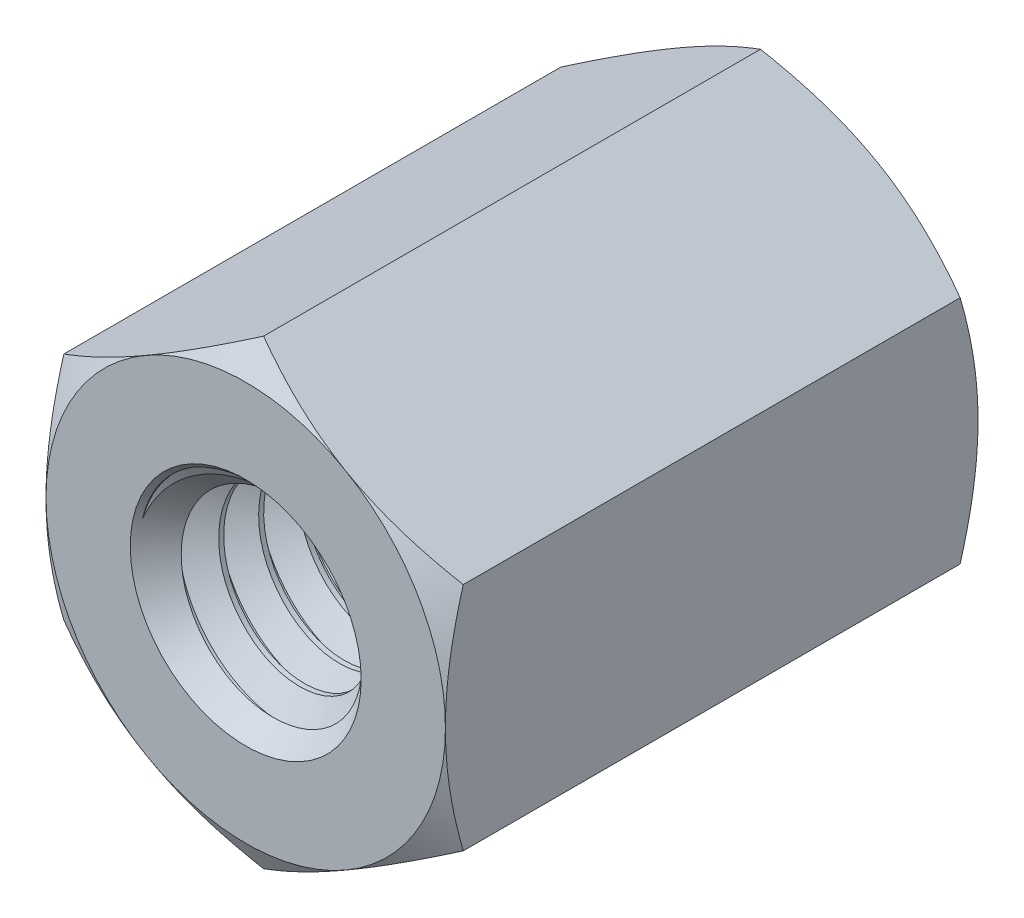
SolidWorks part; units mm, degrees
ref_plane "Front Plane" through (0, 0, 0) normal (0, 0, 1) x (1, 0, 0)
ref_plane "Top Plane" through (0, 0, 0) normal (0, 1, 0) x (1, 0, 0)
ref_plane "Right Plane" through (0, 0, 0) normal (1, 0, 0) x (0, 0, -1)
sketch "Sketch3" plane through (0, 0, 0) normal (1, 0, 0) x (0, 0, -1)
  line L0 (-3, 0) -> (3, 0) construction
  line L1 (0, 2.25) -> (0, -2.25) construction
  line L2 (-3, 1.25) -> (-3, -1.25) construction
  point P2 (-1.8, 0)
  point P3 (1.8, 0)
  dimension "Length" = 6
  dimension "Min Thread Length" = 4.8
  dimension "D1" = 4.8
  dimension "Thread Dia" = 2.5
  dimension "Hex" = 4.5
sketch "Sketch1" plane through (0, 0, 0) normal (0, 0, 1) x (1, 0, 0)
  line L1 (0, 2.5981) -> (-2.25, 1.299)
  line L2 (-2.25, 1.299) -> (-2.25, -1.299)
  line L3 (-2.25, -1.299) -> (0, -2.5981)
  line L4 (0, -2.5981) -> (2.25, -1.299)
  line L5 (2.25, -1.299) -> (2.25, 1.299)
  line L6 (2.25, 1.299) -> (0, 2.5981)
  circle A0 centre (0, 0) radius 2.25 construction
  circle A1 centre (0, 0) radius 1.25
extrude "Extrude1" add sketch "Sketch1" along normal up to vertex (3 mm away) and the other way up to vertex (3 mm away) up to point (0, 0, 3) other way up to point (0, 0, -3)
sketch "Sketch11" plane through (0, 0, -3) normal (0, 0, -1) x (-1, 0, 0)
  circle A0 centre (0, 0) radius 1.25 construction
  circle A1 centre (0, 0) radius 1.25
curve "Helix/Spiral1" pitch 0.45 height 6.45 radius 1.25 centre (0, 0, -3) axis (0, 0, 1) start towards (0, 1, 0) parameters "Pitch"=0.45
sketch "Sketch12" plane through (0, 0, 0) normal (1, 0, 0) x (0, 0, -1)
  line L0 (3.3937, 1.25) -> (3, 1.25)
  line L1 (3.3937, 1.25) -> (3.225, 0.9577)
  line L2 (3.225, 0.9577) -> (3.1687, 0.9577)
  line L3 (3.1687, 0.9577) -> (3, 1.25)
  line L4 (3.1969, 0.9577) -> (3.1969, 1.25) construction
  line L5 (3.3094, 1.1039) -> (3.0844, 1.1039) construction
  dimension "D1" = 0.0563
  dimension "D2" = 0.225
  dimension "D3" = 60
sweep "Sweep1" add profiles "Sketch12" path "Helix/Spiral1"
sketch "Sketch6" plane through (0, 0, -3) normal (0, 0, -1) x (-1, 0, 0)
  line L6 (0, 2.5981) -> (-2.25, 1.299)
  line L7 (-2.25, 1.299) -> (-2.25, -1.299)
  line L8 (-2.25, -1.299) -> (0, -2.5981)
  line L9 (0, -2.5981) -> (2.25, -1.299)
  line L10 (2.25, -1.299) -> (2.25, 1.299)
  line L11 (2.25, 1.299) -> (0, 2.5981)
  line L12 (0, 2.5981) -> (-2.25, 1.299)
  line L13 (-2.25, 1.299) -> (-2.25, -1.299)
  line L14 (-2.25, -1.299) -> (0, -2.5981)
  line L15 (0, -2.5981) -> (2.25, -1.299)
  line L16 (2.25, -1.299) -> (2.25, 1.299)
  line L17 (2.25, 1.299) -> (0, 2.5981)
  dimension "D1" = 0
extrude "Extrude2" cut sketch "Sketch6" along normal through all
sketch "Sketch7" plane through (0, 0, -3) normal (0, 0, -1) x (-1, 0, 0)
  circle A2 centre (0, 0) radius 1.3008
  circle A3 centre (0, 0) radius 1.3008
  dimension "D1" = 0.0508
extrude "Extrude3" cut sketch "Sketch7" against normal through all draft 43
sketch "Sketch8" plane through (0, 0, -3) normal (0, 0, -1) x (-1, 0, 0)
  circle A0 centre (0, 0) radius 2.25 construction
  circle A1 centre (0, 0) radius 2.25
extrude "Extrude4" cut sketch "Sketch8" against normal through all draft 60 flip side to cut
mirror "Mirror1" about plane through (0, 0, 0) normal (0, 0, 1) of "Extrude2", "Extrude3", "Extrude4"
sketch "Sketch9" [suppressed] plane through (0, 0, 0) normal (1, 0, 0) x (0, 0, -1)
  line L1 (-1.2, 1.1353) -> (1.2, 1.1353)
  line L2 (-1.2, 1.1353) -> (-1.2, 0)
  line L3 (-1.2, 0) -> (1.2, 0)
  line L4 (1.2, 1.1353) -> (1.2, 0)
  line L7 (-6, 0) -> (6, 0) construction
revolve "Revolve" [suppressed] add sketch "Sketch9" angle 360 about L0
sketch "Sketch10" [suppressed] plane through (0, 0, 0) normal (1, 0, 0) x (0, 0, -1)
  line L0 (6, 1.25) -> (1.2, 1.25)
  line L1 (-6, 1.25) -> (-1.2, 1.25)
  line L2 (1.2, 1.25) -> (1.2, -1.25)
  line L3 (-6, -1.25) -> (-1.2, -1.25)
  line L4 (-1.2, 1.25) -> (-1.2, -1.25)
  line L5 (1.2, -1.25) -> (6, -1.25)
equation "\"D1@Sketch3\" = \"Min Thread Length@Sketch3\""
equation "\"D3@Helix/Spiral1\" = \"Length@Sketch3\"+\"Pitch@Helix/Spiral1\""
equation "\"D1@Sketch12\" = \"Pitch@Helix/Spiral1\"*.125"
equation "\"D2@Sketch12\" = \"Pitch@Helix/Spiral1\"*.5"
